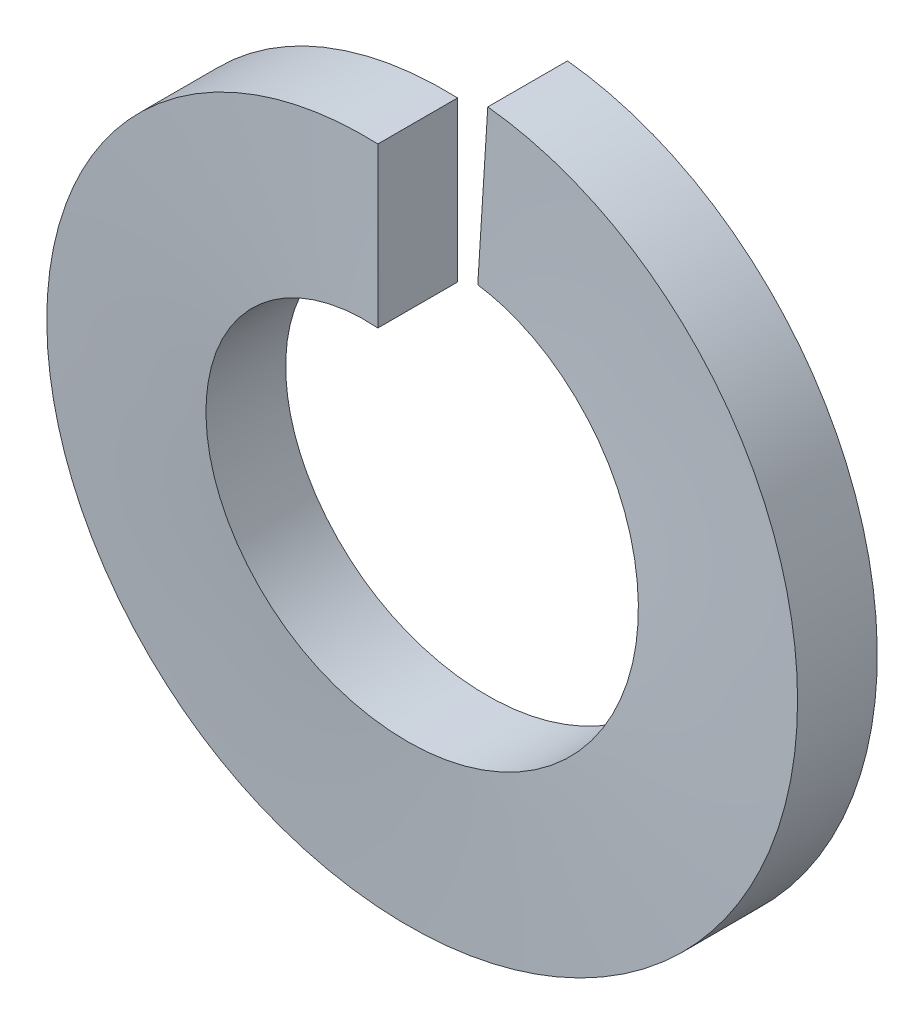
SolidWorks part; units mm, degrees
ref_plane "Front Plane" through (0, 0, 0) normal (0, 0, 1) x (1, 0, 0)
ref_plane "Top Plane" through (0, 0, 0) normal (0, 1, 0) x (1, 0, 0)
ref_plane "Right Plane" through (0, 0, 0) normal (1, 0, 0) x (0, 0, -1)
sketch "Sketch1" plane through (0, 0, 0) normal (0, 0, 1) x (1, 0, 0)
  line L0 (0, 3.1) -> (0, 1.7) construction
  circle A0 centre (0, 0) radius 3.1
  circle A1 centre (0, 0) radius 1.7 construction
  dimension "ID" = 3.4
  dimension "OD" = 6.2
curve "Helix/Spiral1" pitch 0.7778 height 0.77 radius 3.1 left hand yes centre (0, 0, 0) axis (0, 0, -1) start towards (0, 1, 0) parameters "HT"=0.77
sketch "Sketch2" plane through (0, 0, 0) normal (1, 0, 0) x (0, 0, -1)
  line L1 (0, 3.1) -> (-0.7, 3.1)
  line L2 (0, 3.1) -> (0, 1.7)
  line L3 (0, 1.7) -> (-0.7, 1.7)
  line L4 (-0.7, 3.1) -> (-0.7, 1.7)
  dimension "THK" = 0.7
sweep "Sweep1" add profiles "Sketch2" path "Helix/Spiral1"
ref_axis "Center Axis 1" through (0, 0, -2.2957) along (0, 0, 1)
ref_plane "Contact Plane 1" through (0, 0, 0.7) normal (0, 0, 1) x (1, 0, 0)
ref_plane "Contact Plane 2" through (0, 0, -0.7703) normal (0, 0, 1) x (1, 0, 0)
equation "\"HT@Helix/Spiral1\" = \"THK@Sketch2\"*1.1"
